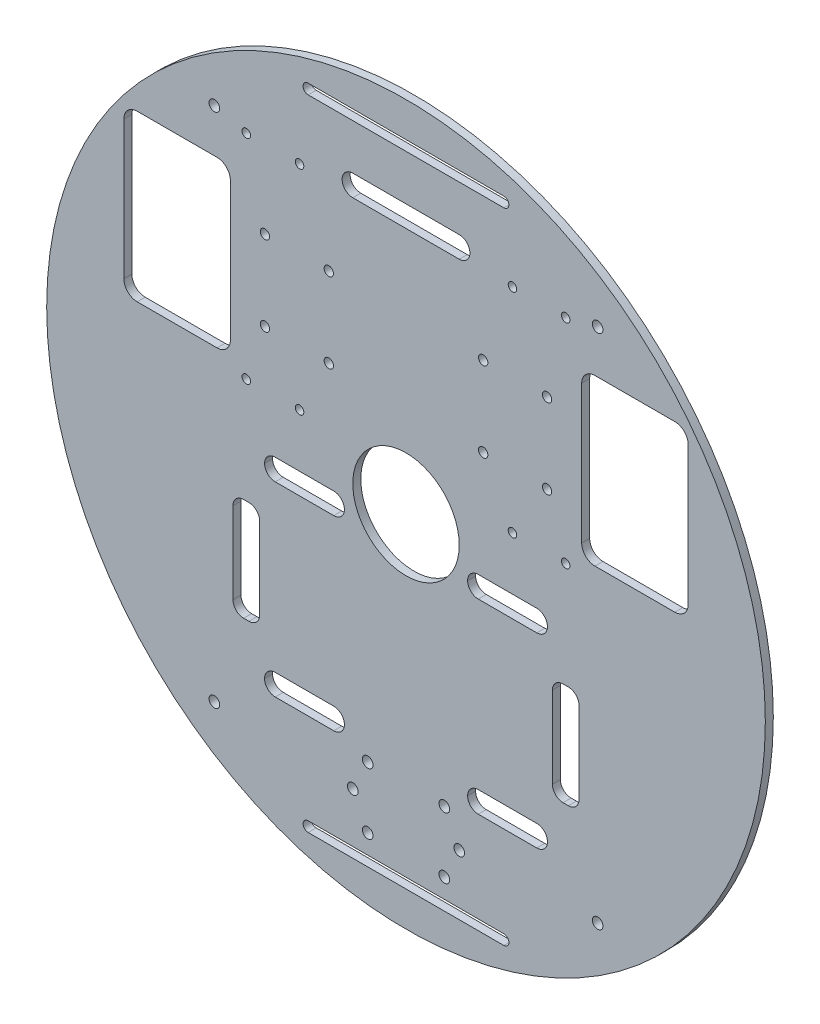
SolidWorks part; units mm, degrees
ref_plane "前视基准面" through (0, 0, 0) normal (0, 0, 1) x (1, 0, 0)
ref_plane "上视基准面" through (0, 0, 0) normal (0, 1, 0) x (1, 0, 0)
ref_plane "右视基准面" through (0, 0, 0) normal (1, 0, 0) x (0, 0, -1)
sketch "草图1" plane through (0, 0, 0) normal (0, 0, 1) x (1, 0, 0)
  line L0 (0, 135) -> (0, -135) construction
  line L1 (0, -99.3042) -> (86, 49.6521) construction
  line L2 (86, 49.6521) -> (-86, 49.6521) construction
  line L3 (-86, 49.6521) -> (0, -99.3042) construction
  line L4 (-106, 80.6521) -> (-66, 80.6521)
  line L5 (-106, 80.6521) -> (-106, 18.6521)
  line L6 (-106, 18.6521) -> (-66, 18.6521)
  line L7 (-66, 80.6521) -> (-66, 18.6521)
  line L8 (-106, 80.6521) -> (-66, 18.6521) construction
  line L9 (-106, 18.6521) -> (-66, 80.6521) construction
  line L10 (106, 80.6521) -> (66, 80.6521)
  line L11 (66, 80.6521) -> (66, 18.6521)
  line L12 (106, 80.6521) -> (66, 18.6521) construction
  line L13 (106, 18.6521) -> (66, 18.6521)
  line L14 (106, 18.6521) -> (66, 80.6521) construction
  line L15 (106, 80.6521) -> (106, 18.6521)
  line L17 (-14.4, -87.8042) -> (14.4, -87.8042) construction
  line L18 (-14.4, -87.8042) -> (-14.4, -110.8042) construction
  line L19 (-14.4, -110.8042) -> (14.4, -110.8042) construction
  line L20 (14.4, -87.8042) -> (14.4, -110.8042) construction
  line L21 (-14.4, -87.8042) -> (14.4, -110.8042) construction
  line L22 (-14.4, -110.8042) -> (14.4, -87.8042) construction
  line L29 (-53, 64.6521) -> (-29, 64.6521) construction
  line L30 (-53, 64.6521) -> (-53, 34.6521) construction
  line L31 (-53, 34.6521) -> (-29, 34.6521) construction
  line L32 (-29, 64.6521) -> (-29, 34.6521) construction
  line L33 (-53, 64.6521) -> (-29, 34.6521) construction
  line L34 (-53, 34.6521) -> (-29, 64.6521) construction
  circle A0 centre (0, 0) radius 135
  circle A1 centre (0, 0) radius 49.6521 construction
  circle A2 centre (-53, 64.6521) radius 1.75
  circle A3 centre (-29, 64.6521) radius 1.75
  circle A4 centre (-53, 34.6521) radius 1.75
  circle A5 centre (-29, 34.6521) radius 1.75
  circle A6 centre (53, 34.6521) radius 1.75
  circle A7 centre (29, 34.6521) radius 1.75
  circle A8 centre (29, 64.6521) radius 1.75
  circle A9 centre (53, 64.6521) radius 1.75
  circle A10 centre (20, -99.3042) radius 2
  circle A11 centre (14.4, -87.8042) radius 2
  circle A12 centre (14.4, -110.8042) radius 2
  circle A13 centre (-14.4, -87.8042) radius 2
  circle A14 centre (-14.4, -110.8042) radius 2
  circle A15 centre (-20, -99.3042) radius 2
  point P25 (0, 49.6521)
  point P26 (-41, 49.6521)
  point P30 (0, 49.6521)
  dimension "D1" = 270
  dimension "D9" = 3.5
  dimension "D10" = 3.5
  dimension "D11" = 3.5
  dimension "D12" = 3.5
  dimension "D14" = 20
  dimension "D2" = 40
  dimension "D3" = 62
  dimension "D4" = 41
  dimension "D5" = 25
  dimension "D6" = 28.8
  dimension "D7" = 24
  dimension "D8" = 30
  dimension "D13" = 23
extrude "凸台-拉伸1" add sketch "草图1" along normal blind 3 contours A0 A14 A9 A7 L10 L15 L13 L11 A2 A3 A4 A5 A6 A8 A10 A11 A12 A13 A15 region at (0, -4.6527, 0)
fillet "圆角1" radius 5 8 edges at (106, 80.6521, 1.5) (66, 80.6521, 1.5) (66, 18.6521, 1.5) (106, 18.6521, 1.5) (-66, 18.6521, 1.5) (-106, 18.6521, 1.5) (-106, 80.6521, 1.5) (-66, 80.6521, 1.5)
sketch "草图2" plane through (0, 0, 3) normal (0, 0, 1) x (1, 0, 0)
  line L0 (0, 0) -> (0, -120) construction
  line L1 (-72, 97) -> (72, 97) construction
  line L2 (-72, 97) -> (-72, -97) construction
  line L3 (-72, -97) -> (72, -97) construction
  line L4 (72, 97) -> (72, -97) construction
  line L5 (-72, 97) -> (72, -97) construction
  line L6 (-72, -97) -> (72, 97) construction
  line L8 (60, -10) -> (-60, -10) construction
  line L9 (60, -10) -> (60, -80) construction
  line L10 (60, -80) -> (-60, -80) construction
  line L11 (-60, -10) -> (-60, -80) construction
  line L12 (60, -10) -> (-60, -80) construction
  line L13 (60, -80) -> (-60, -10) construction
  line L14 (53.1429, -6) -> (23.1429, -6)
  line L15 (53.1429, -6) -> (53.1429, -14)
  line L16 (53.1429, -14) -> (23.1429, -14)
  line L17 (23.1429, -6) -> (23.1429, -14)
  line L18 (53.1429, -6) -> (23.1429, -14) construction
  line L19 (53.1429, -14) -> (23.1429, -6) construction
  line L20 (-23.1429, -6) -> (-53.1429, -6)
  line L21 (-23.1429, -6) -> (-23.1429, -14)
  line L22 (-23.1429, -14) -> (-53.1429, -14)
  line L23 (40, 94) -> (40, 14) construction
  line L24 (-53.1429, -6) -> (-53.1429, -14)
  line L25 (-23.1429, -6) -> (-53.1429, -14) construction
  line L26 (-23.1429, -14) -> (-53.1429, -6) construction
  line L27 (23.1429, -84) -> (53.1429, -84)
  line L28 (23.1429, -84) -> (23.1429, -76)
  line L29 (23.1429, -76) -> (53.1429, -76)
  line L30 (53.1429, -84) -> (53.1429, -76)
  line L31 (23.1429, -84) -> (53.1429, -76) construction
  line L32 (23.1429, -76) -> (53.1429, -84) construction
  line L33 (-23.1429, -84) -> (-53.1429, -84)
  line L34 (-23.1429, -84) -> (-23.1429, -76)
  line L35 (-23.1429, -76) -> (-53.1429, -76)
  line L36 (-53.1429, -84) -> (-53.1429, -76)
  line L37 (-23.1429, -84) -> (-53.1429, -76) construction
  line L38 (-23.1429, -76) -> (-53.1429, -84) construction
  line L39 (65, -25.6876) -> (55, -25.6876)
  line L40 (65, -25.6876) -> (65, -64.3124)
  line L41 (65, -64.3124) -> (55, -64.3124)
  line L42 (55, -25.6876) -> (55, -64.3124)
  line L43 (65, -25.6876) -> (55, -64.3124) construction
  line L44 (65, -64.3124) -> (55, -25.6876) construction
  line L45 (-55, -25.6876) -> (-65, -25.6876)
  line L46 (-55, -25.6876) -> (-55, -64.3124)
  line L47 (-55, -64.3124) -> (-65, -64.3124)
  line L48 (-135, 0) -> (135, 0) construction
  line L49 (-36.7556, -118.1) -> (36.7556, -121.9) construction
  line L50 (-36.7556, 121.9) -> (36.7556, 121.9)
  line L51 (-36.7556, 121.9) -> (-36.7556, 118.1) construction
  line L52 (-36.7556, 118.1) -> (36.7556, 118.1)
  line L53 (36.7556, 121.9) -> (36.7556, 118.1) construction
  line L54 (-36.7556, 121.9) -> (36.7556, 118.1) construction
  line L55 (-36.7556, 118.1) -> (36.7556, 121.9) construction
  line L56 (-36.7556, -121.9) -> (36.7556, -118.1) construction
  line L57 (36.7556, -121.9) -> (36.7556, -118.1) construction
  line L58 (-36.7556, -121.9) -> (-36.7556, -118.1) construction
  line L59 (-36.7556, -118.1) -> (36.7556, -118.1)
  line L60 (-36.7556, -121.9) -> (36.7556, -121.9)
  line L61 (-40, 94) -> (-40, 14) construction
  line L62 (-60, 94) -> (60, 94) construction
  line L63 (-60, 94) -> (-60, 14) construction
  line L64 (-60, 14) -> (60, 14) construction
  line L65 (60, 94) -> (60, 14) construction
  line L66 (-60, 94) -> (60, 14) construction
  line L67 (-60, 14) -> (60, 94) construction
  line L68 (-65, -25.6876) -> (-65, -64.3124)
  line L69 (-55, -25.6876) -> (-65, -64.3124) construction
  line L70 (-55, -64.3124) -> (-65, -25.6876) construction
  line L87 (20, 101) -> (-20, 101)
  line L88 (20, 101) -> (20, 93) construction
  line L89 (20, 93) -> (-20, 93)
  line L90 (-20, 101) -> (-20, 93) construction
  line L91 (20, 101) -> (-20, 93) construction
  line L92 (20, 93) -> (-20, 101) construction
  circle A0 centre (0, 0) radius 20
  circle A1 centre (-72, 97) radius 2
  circle A2 centre (72, 97) radius 2
  circle A3 centre (72, -97) radius 2
  circle A4 centre (-72, -97) radius 2
  circle A17 centre (-60, 94) radius 1.6
  circle A18 centre (-60, 14) radius 1.6
  circle A19 centre (-40, 94) radius 1.6
  circle A20 centre (-40, 14) radius 1.6
  circle A21 centre (60, 14) radius 1.6
  circle A22 centre (60, 94) radius 1.6
  circle A23 centre (40, 94) radius 1.6
  circle A24 centre (40, 14) radius 1.6
  circle A25 centre (0, 0) radius 135 construction
  arc A26 (36.7556, 121.9) -> (36.7556, 118.1) centre (36.7556, 120) cw
  arc A27 (-36.7556, 121.9) -> (-36.7556, 118.1) centre (-36.7556, 120) ccw
  arc A28 (-36.7556, -121.9) -> (-36.7556, -118.1) centre (-36.7556, -120) cw
  arc A29 (36.7556, -121.9) -> (36.7556, -118.1) centre (36.7556, -120) ccw
  arc A36 (20, 101) -> (20, 93) centre (20, 97) cw
  arc A37 (-20, 101) -> (-20, 93) centre (-20, 97) ccw
  point P11 (0, -45)
  point P17 (38.1429, -10)
  point P23 (-38.1429, -10)
  point P25 (0, 54)
  point P29 (38.1429, -80)
  point P34 (-38.1429, -80)
  point P39 (-60, -45)
  point P41 (60, -45)
  point P83 (0, 120)
  point P96 (0, -120)
  dimension "D1" = 144
  dimension "D13" = 3.8
  dimension "D15" = 4
  dimension "D16" = 4
  dimension "D17" = 4
  dimension "D18" = 4
  dimension "D12" = 30
  dimension "D2" = 194
  dimension "D4" = 70
  dimension "D5" = 120
  dimension "D6" = 45
  dimension "D7" = 8
  dimension "D8" = 8
  dimension "D9" = 8
  dimension "D10" = 54
  dimension "D11" = 8
  dimension "D14" = 120
  dimension "D19" = 80
  dimension "D20" = 120
  dimension "D21" = 30
  dimension "D22" = 30
  dimension "D23" = 30
  dimension "D24" = 10
  dimension "D25" = 10
  dimension "D33" = 8
  dimension "D34" = 40
extrude "切除-拉伸1" cut sketch "草图2" against normal blind 10
sketch "草图3" plane through (0, 0, 3) normal (0, 0, 1) x (1, 0, 0)
  line L0 (0, 0) -> (0, -135) construction
  line L1 (0, 93) -> (0, 0) construction
  line L2 (35, -8.8786) -> (-35, -8.8786) construction
  line L3 (35, -8.8786) -> (35, -63.8786) construction
  line L4 (35, -63.8786) -> (-35, -63.8786) construction
  line L5 (-35, -8.8786) -> (-35, -63.8786) construction
  line L6 (35, -8.8786) -> (-35, -63.8786) construction
  line L7 (35, -63.8786) -> (-35, -8.8786) construction
  line L8 (-20, 93) -> (20, 93) construction
  circle A0 centre (0, 0) radius 135 construction
  point P6 (0, -36.3786)
  dimension "D1" = 55
  dimension "D2" = 70
  dimension "D3" = 93
sketch "草图4" plane through (0, 0, 0) normal (0, 0, -1) x (-1, 0, 0)
  line L1 (-88.3346, 51) -> (0, -102)
  line L2 (0, -102) -> (88.3346, 51)
  line L3 (88.3346, 51) -> (-88.3346, 51)
  circle A0 centre (0, 0) radius 102 construction
  point P1 (0, 51)
  dimension "D3" = 204
  dimension "D1" = 176.6692
  dimension "D2" = 153
fillet "圆角2" radius 4 24 edges at (-53.1429, -84, 1.5) (-23.1429, -84, 1.5) (-53.1429, -76, 1.5) (-23.1429, -76, 1.5) (23.1429, -84, 1.5) (23.1429, -76, 1.5) (53.1429, -76, 1.5) (53.1429, -84, 1.5) (-53.1429, -14, 1.5) (-53.1429, -6, 1.5) (-23.1429, -14, 1.5) (-23.1429, -6, 1.5) (23.1429, -14, 1.5) (53.1429, -14, 1.5) (23.1429, -6, 1.5) (53.1429, -6, 1.5) (-55, -64.3124, 1.5) (-65, -64.3124, 1.5) (55, -64.3124, 1.5) (65, -64.3124, 1.5) (-65, -25.6876, 1.5) (-55, -25.6876, 1.5) (65, -25.6876, 1.5) (55, -25.6876, 1.5)
